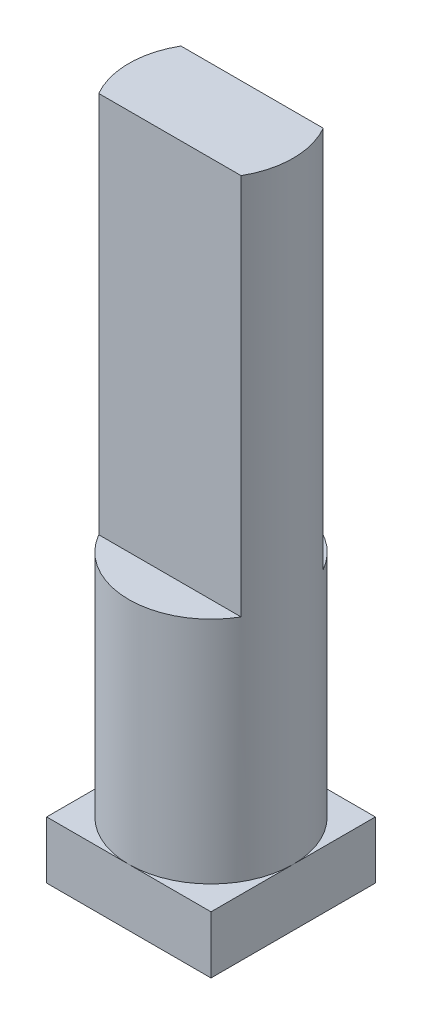
SolidWorks part; units mm, degrees
ref_plane "Front Plane" through (0, 0, 0) normal (0, 0, 1) x (1, 0, 0)
ref_plane "Top Plane" through (0, 0, 0) normal (0, 1, 0) x (1, 0, 0)
ref_plane "Right Plane" through (0, 0, 0) normal (1, 0, 0) x (0, 0, -1)
sketch "Sketch1" plane through (0, 0, 0) normal (0, 1, 0) x (1, 0, 0)
  line L0 (-4.3, 4.3) -> (4.3, 4.3)
  line L1 (-4.5, -4.5) -> (4.5, -4.5) construction
  line L2 (-4.5, -4.5) -> (-4.5, 4.5) construction
  line L3 (-4.5, 4.5) -> (4.5, 4.5) construction
  line L4 (4.5, -4.5) -> (4.5, 4.5) construction
  line L5 (4.3, -4.3) -> (4.3, 4.3)
  line L6 (-4.3, -4.3) -> (4.3, -4.3)
  line L7 (-4.3, -4.3) -> (-4.3, 4.3)
  point P0 (0, 0)
  dimension "D1" = 9
  dimension "D2" = 9
  dimension "D3" = 0.2
extrude "Boss-Extrude1" add sketch "Sketch1" along normal blind 3
sketch "Sketch2" plane through (0, 3, 0) normal (0, 1, 0) x (1, 0, 0)
  line L0 (-4.3, 4.3) -> (4.3, -4.3) construction
  line L1 (4.3, 4.3) -> (-4.3, -4.3) construction
  circle A0 centre (0, 0) radius 4.3
extrude "Boss-Extrude2" add sketch "Sketch2" along normal blind 32
sketch "Sketch3" plane through (0, 3, 0) normal (0, 1, 0) x (1, 0, 0)
  circle A0 centre (0, 0) radius 1.6
  circle A1 centre (0, 0) radius 2
extrude "Cut-Extrude1" [suppressed] cut sketch "Sketch3" along normal blind 3 from offset 7.6
sketch "Sketch4" plane through (0, 35, 0) normal (0, 1, 0) x (1, 0, 0)
  line L0 (0, 4.3) -> (0, 0) construction
  line L1 (-4.3, 0) -> (4.3, 0) construction
  line L2 (0, 2.15) -> (-3.7239, 2.15)
  line L3 (0, 2.15) -> (3.7239, 2.15)
  line L4 (0, -2.15) -> (-3.7239, -2.15)
  line L5 (0, -2.15) -> (3.7239, -2.15)
  circle A0 centre (0, 0) radius 4.3 construction
  circle A1 centre (0, 0) radius 4.3 construction
  arc A2 (-3.7239, 2.15) -> (3.7239, 2.15) centre (0, 0) cw
  arc A3 (-3.7239, -2.15) -> (3.7239, -2.15) centre (0, 0) ccw
extrude "Cut-Extrude2" cut sketch "Sketch4" against normal blind 20
fillet "Fillet1" [suppressed] radius 1
sketch "Sketch5" plane through (0, 35, 0) normal (0, 1, 0) x (1, 0, 0)
  line L2 (-3.7239, -2.15) -> (3.7239, -2.15)
  line L3 (3.7239, 2.15) -> (-3.7239, 2.15)
  line L4 (-3.7239, -2.15) -> (3.7239, -2.15)
  line L5 (3.7239, 2.15) -> (-3.7239, 2.15)
  arc A2 (3.7239, -2.15) -> (3.7239, 2.15) centre (0, 0) ccw
  arc A3 (-3.7239, 2.15) -> (-3.7239, -2.15) centre (0, 0) ccw
  arc A4 (3.7239, -2.15) -> (3.7239, 2.15) centre (0, 0) ccw
  arc A5 (-3.7239, 2.15) -> (-3.7239, -2.15) centre (0, 0) ccw
  dimension "D1" = 0
